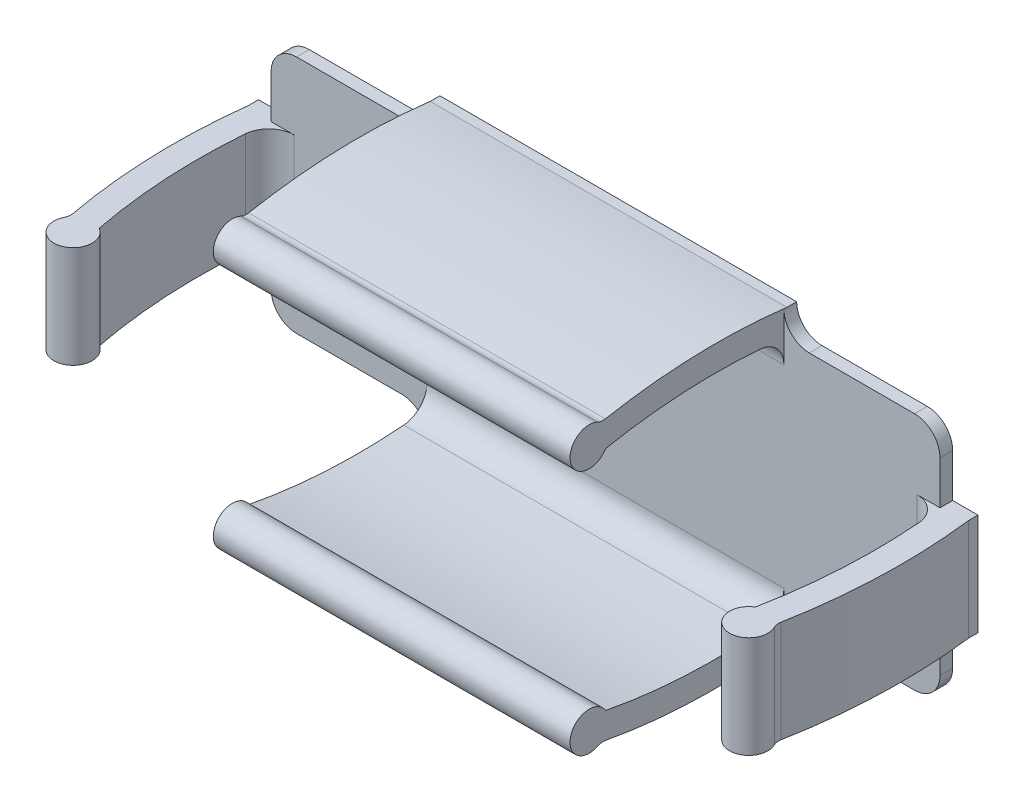
SolidWorks part; units mm, degrees
material "Part template material"
ref_plane "Top Plane" through (0, 0, 0) normal (0, 0, 1) x (1, 0, 0)
ref_plane "Right Plane" through (0, 0, 0) normal (0, 1, 0) x (1, 0, 0)
ref_plane "Front Plane" through (0, 0, 0) normal (1, 0, 0) x (0, 0, -1)
sketch "Sketch1" plane through (0, 0, 0) normal (0, 0, 1) x (1, 0, 0)
  line L1 (26.25, -9.4) -> (-26.25, -9.4)
  line L2 (26.25, -9.4) -> (26.25, 9.4)
  line L3 (26.25, 9.4) -> (-26.25, 9.4)
  line L4 (-26.25, -9.4) -> (-26.25, 9.4)
  line L5 (26.25, -9.4) -> (-26.25, 9.4) construction
  line L6 (26.25, 9.4) -> (-26.25, -9.4) construction
  point P0 (0, 0)
  dimension "D1" = 18.8
  dimension "D2" = 52.5
extrude "Boss-Extrude1" add sketch "Sketch1" along normal blind 1
sketch "Sketch2" plane through (0, 0, 0) normal (0, 1, 0) x (1, 0, 0)
  line L1 (-26.25, 0) -> (-26.25, -1)
  line L2 (-26.25, 0) -> (-28.2355, 0)
  line L3 (-28.2355, 0) -> (-28.2355, -0.7596)
  arc A0 (-26.25, -1) -> (-25.75, -14.9911) centre (18.4239, -6.408) ccw
  arc A1 (-28.2355, -0.7596) -> (-27.7133, -15.3725) centre (18.4239, -6.408) ccw
  arc A2 (-27.7133, -15.3725) -> (-25.75, -14.9911) centre (-26.5184, -16.2793) ccw
  dimension "D3" = 45
  dimension "D5" = 1.5
  dimension "D1" = 14
  dimension "D2" = 0.5
  dimension "D4" = 2
extrude "Boss-Extrude2" add sketch "Sketch2" along normal mid plane 8
mirror "Mirror1" about plane through (0, 0, 0) normal (1, 0, 0) of "Boss-Extrude2"
sketch "Sketch3" plane through (0, 0, 0) normal (1, 0, 0) x (0, 0, -1)
  line L1 (0, 9.4) -> (-1, 9.4)
  line L3 (-0.7594, 11.3855) -> (0, 11.3855)
  line L4 (0, 11.3855) -> (0, 9.4)
  arc A0 (-1, 9.4) -> (-15, 8.9) centre (-6.4135, -35.2732) ccw
  arc A1 (-0.7594, 11.3855) -> (-15.3816, 10.8633) centre (-6.4135, -35.2732) ccw
  arc A2 (-15.3816, 10.8633) -> (-15, 8.9) centre (-16.2883, 9.6683) ccw
  dimension "D3" = 45
  dimension "D5" = 1.5
  dimension "D1" = 0.5
  dimension "D2" = 14
  dimension "D4" = 2
extrude "Boss-Extrude3" add sketch "Sketch3" along normal mid plane 28
mirror "Mirror2" about plane through (0, 0, 0) normal (0, 1, 0) of "Boss-Extrude3"
fillet "Fillet1" radius 2 8 edges at (0, 9.4, 1) (-26.25, 0, 1) (0, -9.4, 1) (26.25, 0, 1) (26.25, -9.4, 0.5) (26.25, 9.4, 0.5) (-26.25, -9.4, 0.5) (-26.25, 9.4, 0.5)
fillet "Fillet2" radius 2 4 edges at (-14, -9.4, 0.5) (14, -9.4, 0.5) (14, 9.4, 0.5) (-14, 9.4, 0.5)
fillet "Fillet3" radius 1 4 edges at (-27.7133, 0, 15.3725) (0, -10.8633, 15.3816) (0, 10.8633, 15.3816) (27.7133, 0, 15.3725)
